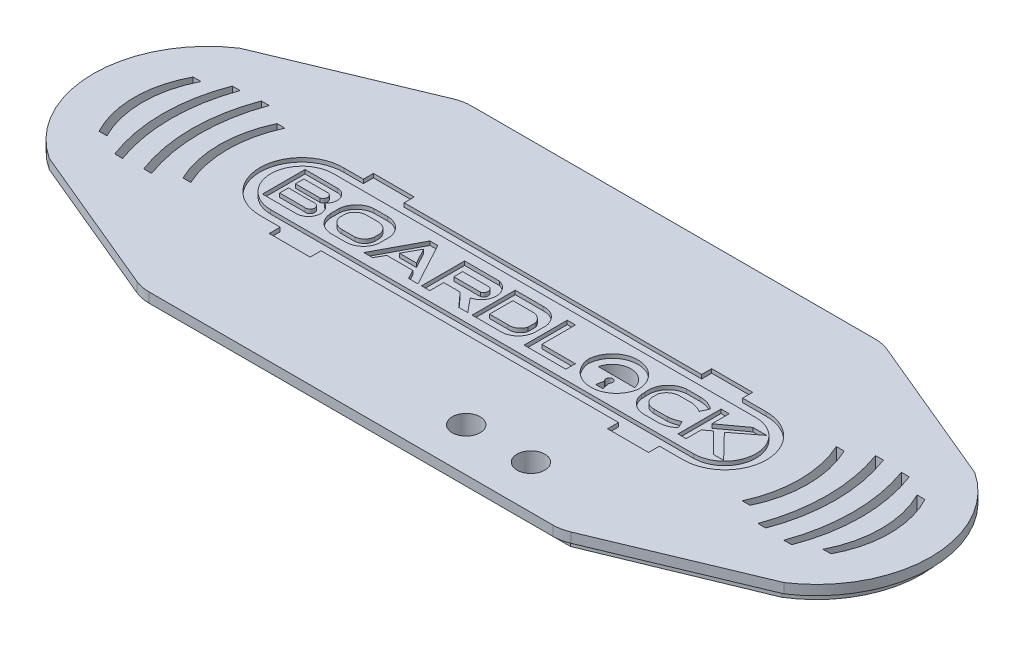
SolidWorks part; units mm, degrees
ref_plane "Front Plane" through (0, 0, 0) normal (0, 0, 1) x (1, 0, 0)
ref_plane "Top Plane" through (0, 0, 0) normal (0, 1, 0) x (1, 0, 0)
ref_plane "Right Plane" through (0, 0, 0) normal (1, 0, 0) x (0, 0, -1)
sketch "Sketch2" plane through (0, 0, 0) normal (0, 1, 0) x (1, 0, 0)
  line L0 (0, 0) -> (102, 0) construction
  line L1 (0, 0) -> (0, -77.2) construction
  line L2 (102, 0) -> (102, -77.2) construction
  line L3 (0, -77.2) -> (102, -77.2) construction
  line L4 (51, 0) -> (51, -77.2) construction
  line L5 (0, -38.6) -> (102, -38.6) construction
  line L6 (-2.5, 2.5) -> (104.5, 2.5)
  line L7 (-2.5, -79.7) -> (104.5, -79.7)
  line L8 (104.5, 2.5) -> (144.7372, -14.2911)
  line L9 (104.5, -79.7) -> (144.7372, -62.9089)
  line L10 (102, -38.6) -> (155.3, -38.6) construction
  line L11 (-2.5, -79.7) -> (-42.7372, -62.9089)
  line L12 (-2.5, 2.5) -> (-42.7372, -14.2911)
  line L13 (0, 0) -> (102, 0)
  line L14 (102, 0) -> (104.5, 0)
  line L15 (104.5, 0) -> (142.7026, -15.7437)
  line L16 (104.5, -77.2) -> (142.7026, -61.4563)
  line L17 (102, -77.2) -> (104.5, -77.2)
  line L18 (-2.5, -77.2) -> (-40.7026, -61.4563)
  line L19 (0, -77.2) -> (-2.5, -77.2)
  line L20 (-2.5, 0) -> (-40.7026, -15.7437)
  line L21 (0, 0) -> (-2.5, 0)
  line L22 (0, -77.2) -> (102, -77.2)
  line L23 (0.5, 0) -> (0.5, -77.2) construction
  line L24 (0, -76.7) -> (97.7329, -76.7) construction
  line L25 (0.5, -74.6) -> (97.3633, -74.6) construction
  line L26 (63.32, -77.2) -> (63.32, 0) construction
  line L27 (0.5, -62.6) -> (97.044, -62.6) construction
  line L28 (75.32, -62.6) -> (75.32, -74.6) construction
  line L29 (79.83, -62.6) -> (79.83, -74.6) construction
  line L30 (91.83, -62.6) -> (91.83, -74.6) construction
  line L31 (69.32, -62.6) -> (69.32, -74.6) construction
  line L32 (63.32, -68.6) -> (75.32, -68.6) construction
  line L33 (85.83, -62.6) -> (85.83, -74.6) construction
  line L34 (79.83, -68.6) -> (91.83, -68.6) construction
  arc A0 (144.7372, -14.2911) -> (144.7372, -62.9089) centre (128.65, -38.6) cw
  arc A1 (-42.7372, -14.2911) -> (-42.7372, -62.9089) centre (-26.65, -38.6) ccw
  arc A2 (142.7026, -15.7437) -> (142.7026, -61.4563) centre (128.65, -38.6) cw
  arc A3 (-40.7026, -15.7437) -> (-40.7026, -61.4563) centre (-26.65, -38.6) ccw
  circle A4 centre (69.32, -68.6) radius 3.55
  circle A5 centre (85.83, -68.6) radius 3.55
  point P16 (157.8, -38.6)
  dimension "D3" = 2.5
  dimension "D10" = 2.5
  dimension "D1" = 77.2
  dimension "D2" = 102
  dimension "D4" = 2.5
  dimension "D5" = 2.5
  dimension "D6" = 2.5
  dimension "D7" = 0.5
  dimension "D8" = 2.5
  dimension "D9" = 53.3
  dimension "D11" = 0.5
  dimension "D12" = 2.1
  dimension "D13" = 62.82
  dimension "D14" = 12
  dimension "D15" = 12
  dimension "D16" = 4.51
  dimension "D17" = 12
  dimension "D18" = 6
  dimension "D19" = 6
  dimension "D20" = 6
  dimension "D21" = 6
extrude "Boss-Extrude3" add sketch "Sketch2" along normal blind 2.5 contours L6 L8 A0 L9 L7 L11 A1 L12
extrude "Boss-Extrude4" add sketch "Sketch2<8>" against normal blind 2.5 contours L20 A3 L18 L19 L22 L17 L16 A2 L15 L14 L13 L21 region at (50.8464, 0, 38.4266)
sketch "Sketch2<8>" plane through (0, 0, 0) normal (0, 1, 0) x (1, 0, 0) same geometry as "Sketch2"
sketch "Sketch3" plane through (0, 2.5, 0) normal (0, 1, 0) x (1, 0, 0)
  line L0 (-55.8, -38.6) -> (157.8, -38.6) construction
  line L1 (51, 2.5) -> (51, -79.7) construction
  line L2 (-2.5, 2.5) -> (104.5, 2.5) construction
  line L3 (-2.5, -79.7) -> (104.5, -79.7) construction
  line L4 (201.4283, 144.6262) -> (1084.095, 144.6262) construction
  line L5 (-2.9873, -27.462) -> (1.9495, -27.462)
  line L6 (1.9495, -27.462) -> (1.9495, -24.9021)
  line L7 (1.9495, -24.9021) -> (12.3717, -24.9021)
  line L8 (12.3717, -24.9021) -> (12.3717, -27.462)
  line L9 (12.3717, -27.462) -> (88.2398, -27.462)
  line L10 (88.2398, -27.462) -> (88.2398, -24.9021)
  line L11 (88.2398, -24.9021) -> (98.6886, -24.9021)
  line L12 (98.6886, -24.9021) -> (98.6886, -27.462)
  line L13 (98.6886, -27.462) -> (104.6245, -27.462)
  line L14 (104.6245, -48.6746) -> (98.6886, -48.6746)
  line L15 (98.6886, -48.6746) -> (98.6886, -51.4646)
  line L16 (98.6886, -51.4646) -> (88.2398, -51.4646)
  line L17 (88.2398, -51.4646) -> (88.2398, -48.6746)
  line L18 (88.2398, -48.6746) -> (12.3717, -48.6746)
  line L19 (12.3717, -48.6746) -> (12.3717, -51.4646)
  line L20 (12.3717, -51.4646) -> (1.9495, -51.4646)
  line L21 (1.9495, -51.4646) -> (1.9495, -48.6746)
  line L22 (1.9495, -48.6746) -> (-2.9873, -48.6746)
  line L23 (-2.9873, -30.0692) -> (104.7002, -30.0692)
  line L24 (104.7002, -46.0158) -> (-3.1948, -46.0158)
  line L25 (-7.6306, -32.7625) -> (-7.6306, -43.6232)
  line L26 (-7.6306, -43.6232) -> (1.1441, -43.6232)
  line L27 (-7.6306, -32.7625) -> (0.7133, -32.7625)
  line L28 (5.3465, -39.2139) -> (5.3465, -36.9174)
  line L29 (-5.6807, -35.0072) -> (0.6, -35.0072)
  line L30 (-5.6807, -35.0072) -> (-5.6807, -37.1385)
  line L31 (-5.6807, -37.1385) -> (0.6, -37.1385)
  line L33 (-5.6807, -38.9524) -> (0.7133, -38.9524)
  line L34 (-5.6807, -38.9524) -> (-5.6807, -41.1744)
  line L35 (-5.6807, -41.1744) -> (0.7133, -41.1744)
  line L41 (10.1371, -35.0072) -> (13.3467, -35.0072)
  line L42 (9.866, -32.6184) -> (13.2281, -32.6184)
  line L43 (18.2229, -43.6232) -> (20.4629, -43.6232)
  line L44 (18.0967, -36.7888) -> (18.0967, -39.563)
  line L45 (16.1379, -37.4286) -> (16.1379, -38.7874)
  line L46 (13.8283, -43.6232) -> (10.2518, -43.6232)
  line L47 (20.4629, -43.6232) -> (21.7662, -41.3167)
  line L48 (13.6087, -41.3167) -> (10.2917, -41.3167)
  line L49 (21.7662, -41.3167) -> (28.4046, -41.3167)
  line L50 (7.3404, -38.9659) -> (7.3404, -37.4286)
  line L51 (28.4046, -41.3167) -> (29.6467, -43.6232)
  line L52 (29.6467, -43.6232) -> (32.0292, -43.6232)
  line L53 (32.0292, -43.6232) -> (26.1026, -32.6184)
  line L54 (26.1026, -32.6184) -> (24.0876, -32.6184)
  line L55 (24.0876, -32.6184) -> (18.2229, -43.6232)
  line L56 (22.9065, -39.2139) -> (27.2439, -39.2139)
  line L57 (27.2439, -39.2139) -> (25.0951, -35.224)
  line L58 (25.0951, -35.224) -> (22.9065, -39.2139)
  line L59 (32.928, -32.6184) -> (32.928, -43.6232)
  line L60 (32.928, -43.6232) -> (35.043, -43.6232)
  line L61 (35.043, -43.6232) -> (35.043, -40.0634)
  line L62 (35.043, -40.0634) -> (39.244, -40.0634)
  line L63 (39.244, -40.0634) -> (42.431, -43.6232)
  line L64 (42.431, -43.6232) -> (44.7378, -43.6232)
  line L65 (44.7378, -43.6232) -> (41.7936, -40.0634)
  line L66 (32.928, -32.6184) -> (41.7936, -32.6184)
  line L67 (35.043, -35.224) -> (35.043, -37.4805)
  line L68 (35.043, -37.4805) -> (41.7936, -37.4805)
  line L69 (35.043, -35.224) -> (41.7936, -35.224)
  line L70 (45.8463, -32.6184) -> (45.8463, -43.6232)
  line L71 (45.8463, -43.6232) -> (52.8329, -43.6232)
  line L72 (45.8463, -32.6184) -> (52.9687, -32.6184)
  line L73 (57.6458, -36.7888) -> (57.6458, -39.563)
  line L74 (47.8647, -35.224) -> (47.8647, -41.1744)
  line L75 (47.8647, -41.1744) -> (52.6, -41.1744)
  line L76 (47.8647, -35.224) -> (52.6, -35.224)
  line L77 (55.6246, -37.1385) -> (55.6246, -39.1866)
  line L78 (59.1096, -32.6184) -> (59.1096, -43.6232)
  line L79 (59.1096, -43.6232) -> (69.7525, -43.6232)
  line L80 (69.7525, -43.6232) -> (69.7525, -41.1876)
  line L81 (69.7525, -41.1876) -> (61.1954, -41.1876)
  line L82 (61.1954, -41.1876) -> (61.1954, -32.6184)
  line L83 (61.1954, -32.6184) -> (59.1096, -32.6184)
  line L84 (72.3273, -37.9056) -> (81.6057, -37.9056)
  line L85 (76.285, -40.2528) -> (75.9572, -42.1923)
  line L86 (75.9572, -42.1923) -> (77.8461, -42.1923)
  line L87 (77.8461, -42.1923) -> (77.3335, -40.2528)
  line L88 (90.3322, -35.0072) -> (93.3549, -35.0072)
  line L89 (96.0824, -35.9398) -> (96.9798, -33.9561)
  line L90 (92.9888, -32.6184) -> (89.5293, -32.6184)
  line L91 (86.9671, -37.333) -> (86.9671, -38.6)
  line L92 (86.9671, -38.6) -> (86.9671, -39.0585)
  line L93 (89.7665, -41.1876) -> (93.2664, -41.1876)
  line L94 (96.1597, -40.3804) -> (97.0399, -42.1923)
  line L95 (93.0498, -43.6232) -> (90.1278, -43.6232)
  line L96 (84.9417, -38.6) -> (84.9417, -39.5139)
  line L97 (98.3461, -32.6195) -> (98.3461, -43.6259)
  line L98 (98.3461, -43.6259) -> (100.4335, -43.6259)
  line L99 (100.4335, -43.6259) -> (100.4335, -39.7387)
  line L100 (100.4335, -39.7387) -> (102.2231, -38.4318)
  line L101 (102.2231, -38.4318) -> (107.3754, -43.6259)
  line L102 (107.3754, -43.6259) -> (110.0073, -43.6259)
  line L103 (110.0073, -43.6259) -> (103.904, -37.333)
  line L104 (103.904, -37.333) -> (110.0073, -32.6195)
  line L105 (110.0073, -32.6195) -> (106.4905, -32.6195)
  line L106 (106.4905, -32.6195) -> (100.4335, -37.0424)
  line L107 (100.4335, -37.0424) -> (100.4335, -32.6195)
  line L108 (100.4335, -32.6195) -> (98.3461, -32.6195)
  arc A0 (86.9671, -37.333) -> (90.3322, -35.0072) centre (90.1278, -38.3088) cw
  arc A1 (93.3549, -35.0072) -> (96.0824, -35.9398) centre (92.5616, -41.7819) cw
  arc A2 (-42.7372, -14.2911) -> (-42.7372, -62.9089) centre (-26.65, -38.6) ccw construction
  arc A3 (144.7372, -62.9089) -> (144.7372, -14.2911) centre (128.65, -38.6) ccw construction
  arc A4 (-2.9873, -27.462) -> (-2.9873, -48.6746) centre (-3.1948, -38.0683) ccw
  arc A5 (104.6245, -27.462) -> (104.6245, -48.6746) centre (104.776, -38.0683) cw
  arc A6 (-2.9873, -30.0692) -> (-3.1948, -46.0158) centre (-3.091, -38.0425) ccw
  arc A7 (104.7002, -30.0692) -> (104.7002, -46.0158) centre (104.7002, -38.0425) cw
  arc A8 (0.7133, -32.7625) -> (2.2325, -37.6827) centre (0.6, -35.492) cw
  arc A9 (1.1441, -43.6232) -> (2.2325, -37.6827) centre (1.0303, -40.5324) ccw
  arc A10 (0.6, -35.0072) -> (0.6, -37.1385) centre (0.3019, -36.0728) cw
  arc A11 (0.7133, -41.1744) -> (0.7133, -38.9524) centre (0.9838, -40.0634) ccw
  arc A12 (5.3465, -36.9174) -> (9.866, -32.6184) centre (10.1371, -37.4286) cw
  arc A13 (18.0967, -36.7888) -> (13.2281, -32.6184) centre (13.2836, -37.4805) ccw
  arc A14 (5.3465, -39.2139) -> (10.2518, -43.6232) centre (10.0037, -38.9659) ccw
  arc A15 (13.8283, -43.6232) -> (18.0967, -39.563) centre (13.6087, -39.1187) ccw
  arc A16 (10.1371, -35.0072) -> (7.3404, -37.4286) centre (10.2483, -37.9613) ccw
  arc A17 (13.3467, -35.0072) -> (16.1379, -37.4286) centre (13.2781, -37.9056) cw
  arc A18 (16.1379, -38.7874) -> (13.6087, -41.3167) centre (13.3904, -38.5692) cw
  arc A19 (10.2917, -41.3167) -> (7.3404, -38.9659) centre (10.2917, -38.2887) cw
  arc A20 (41.7936, -35.224) -> (41.7936, -37.4805) centre (41.488, -36.3523) cw
  arc A21 (41.7936, -40.0634) -> (41.7936, -32.6184) centre (40.9073, -36.3409) ccw
  arc A22 (52.9687, -32.6184) -> (57.6458, -36.7888) centre (53.222, -37.0421) cw
  arc A23 (57.6458, -39.563) -> (52.8329, -43.6232) centre (53.2093, -39.1866) cw
  arc A24 (52.6, -35.224) -> (55.6246, -37.1385) centre (52.8789, -38.1299) cw
  arc A25 (55.6246, -39.1866) -> (52.6, -41.1744) centre (52.8755, -38.2986) cw
  arc A26 (70.3877, -38.6) -> (83.4404, -38.6) centre (76.9141, -38.8997) cw
  arc A27 (70.3877, -38.6) -> (83.4404, -38.6) centre (76.9141, -37.8504) ccw
  arc A28 (76.285, -40.2528) -> (77.3335, -40.2528) centre (76.8092, -39.581) cw
  arc A29 (72.3273, -37.9056) -> (81.6057, -37.9056) centre (76.9665, -38.9919) cw
  arc A30 (96.9798, -33.9561) -> (92.9888, -32.6184) centre (93.0498, -39.0585) ccw
  arc A31 (89.5293, -32.6184) -> (84.9417, -38.6) centre (89.9999, -37.7293) ccw
  arc A32 (86.9671, -39.0585) -> (89.7665, -41.1876) centre (89.6538, -38.4308) ccw
  arc A33 (93.2664, -41.1876) -> (96.1597, -40.3804) centre (92.4973, -32.8415) ccw
  arc A34 (84.9417, -39.5139) -> (90.1278, -43.6232) centre (89.7907, -38.7214) ccw
  arc A35 (93.0498, -43.6232) -> (97.0399, -42.1923) centre (93.1901, -37.7354) ccw
extrude "Logo" cut sketch "Sketch3" against normal blind 1 contours L26 A9 A8 L27 L25 A11 L35 L34 L33 L29 A10 L31 L30 | L46 A15 L44 A13 L42 A12 L28 A14 L48 A19 L50 A16 L41 A17 L45 A18 | L54 L55 L43 L47 L49 L51 L52 L53 L58 L57 L56 | L65 A21 L66 L59 L60 L61 L62 L63 L64 L69 A20 L68 L67 | A23 L73 A22 L72 L70 L71 L77 A25 L75 L74 L76 A24 | A26 A27 L85 A28 L87 L86 L84 A29 | L95 A35 L94 A33 L93 A32 L92 L91 A0 L88 A1 L89 A30 L90 A31 L96 A34 | L107 L108 L97 L98 L99 L100 L101 L102 L103 L104 L105 L106 | L82 L83 L78 L79 L80 L81 | A4 L22 L21 L20 L19 L18 L17 L16 L15 L14 A5 L13 L12 L11 L10 L9 L8 L7 L6 L5 | A6 L24 A7 L23 | L78 L79 L80 L81 L82 L83 region at (-2.2321, 2.5, 38.3038) region at (5.5149, 2.5, 38.0657) region at (21.3111, 2.5, 38.2038) region at (37.3608, 2.5, 32.7798) region at (49.4075, 2.5, 32.7799) region at (60.1525, 2.5, 32.7715) region at (88.1536, 2.5, 35.4525) region at (102.8661, 2.5, 37.8921) region at (76.9141, 2.5, 32.5442)
fillet "Fillet1" radius 10 4 edges at (-2.5, 1.25, -2.5) (104.5, 1.25, -2.5) (104.5, 1.25, 79.7) (-2.5, 1.25, 79.7)
sketch "Sketch4" plane through (0, 2.5, 0) normal (0, 1, 0) x (1, 0, 0)
  line L0 (-55.8, -38.6) -> (157.8, -38.6) construction
  line L1 (51, 2.5) -> (51, -79.7) construction
  line L2 (-0.4972, 2.5) -> (102.4972, 2.5) construction
  line L3 (-0.4972, -79.7) -> (102.4972, -79.7) construction
  line L4 (-42.3364, -26.6) -> (-42.3364, -50.6) construction
  line L5 (-40.3364, -26.6) -> (-40.3364, -50.6) construction
  line L6 (-35.3364, -23.6) -> (-35.3364, -53.6) construction
  line L7 (-33.3364, -23.6) -> (-33.3364, -53.6) construction
  line L8 (-28.3364, -23.2) -> (-28.3364, -53.2) construction
  line L9 (-26.3364, -23.2) -> (-26.3364, -53.2) construction
  line L10 (-21.3364, -26.2) -> (-21.3364, -50.2) construction
  line L11 (-19.3364, -26.2) -> (-19.3364, -50.2) construction
  line L12 (-42.3364, -26.6) -> (-40.3364, -26.6)
  line L13 (-42.3364, -50.6) -> (-40.3364, -50.6)
  line L14 (-35.3364, -53.6) -> (-33.3364, -53.6)
  line L15 (-35.3364, -23.6) -> (-33.3364, -23.6)
  line L16 (-28.3364, -23.2) -> (-26.3364, -23.2)
  line L17 (-28.3364, -53.2) -> (-26.3364, -53.2)
  line L18 (-21.3364, -50.2) -> (-19.3364, -50.2)
  line L19 (-21.3364, -26.2) -> (-19.3364, -26.2)
  line L20 (121.3364, -26.2) -> (121.3364, -50.2) construction
  line L21 (123.3364, -26.2) -> (123.3364, -50.2) construction
  line L22 (128.3364, -23.2) -> (128.3364, -53.2) construction
  line L23 (130.3364, -23.2) -> (130.3364, -53.2) construction
  line L24 (135.3364, -23.6) -> (135.3364, -53.6) construction
  line L25 (137.3364, -23.6) -> (137.3364, -53.6) construction
  line L26 (142.3364, -26.6) -> (142.3364, -50.6) construction
  line L27 (144.3364, -26.6) -> (144.3364, -50.6) construction
  line L28 (123.3364, -26.2) -> (121.3364, -26.2)
  line L29 (123.3364, -50.2) -> (121.3364, -50.2)
  line L30 (130.3364, -53.2) -> (128.3364, -53.2)
  line L31 (130.3364, -23.2) -> (128.3364, -23.2)
  line L32 (137.3364, -23.6) -> (135.3364, -23.6)
  line L33 (137.3364, -53.6) -> (135.3364, -53.6)
  line L34 (144.3364, -50.6) -> (142.3364, -50.6)
  line L35 (144.3364, -26.6) -> (142.3364, -26.6)
  arc A0 (-42.7372, -14.2911) -> (-42.7372, -62.9089) centre (-26.65, -38.6) ccw construction
  arc A1 (144.7372, -62.9089) -> (144.7372, -14.2911) centre (128.65, -38.6) ccw construction
  arc A2 (-42.3364, -26.6) -> (-42.3364, -50.6) centre (-19.91, -38.6) ccw
  arc A3 (-40.3364, -26.6) -> (-40.3364, -50.6) centre (-16.7181, -38.6) ccw
  arc A4 (-35.3364, -23.6) -> (-35.3364, -53.6) centre (3.8054, -38.6) ccw
  arc A5 (-33.3364, -53.6) -> (-33.3364, -23.6) centre (8.2465, -38.6) cw
  arc A6 (-28.3364, -23.2) -> (-28.3364, -53.2) centre (11.3609, -38.2) ccw
  arc A7 (-26.3364, -23.2) -> (-26.3364, -53.2) centre (14.8909, -38.2) ccw
  arc A8 (-21.3364, -26.2) -> (-21.3364, -50.2) centre (3.9499, -38.2) ccw
  arc A9 (-19.3364, -26.2) -> (-19.3364, -50.2) centre (6.9686, -38.2) ccw
  arc A10 (121.3364, -26.2) -> (121.3364, -50.2) centre (95.0314, -38.2) cw
  arc A11 (123.3364, -26.2) -> (123.3364, -50.2) centre (98.0501, -38.2) cw
  arc A12 (128.3364, -23.2) -> (128.3364, -53.2) centre (87.1091, -38.2) cw
  arc A13 (130.3364, -23.2) -> (130.3364, -53.2) centre (90.6391, -38.2) cw
  arc A14 (135.3364, -53.6) -> (135.3364, -23.6) centre (93.7535, -38.6) ccw
  arc A15 (137.3364, -23.6) -> (137.3364, -53.6) centre (98.1946, -38.6) cw
  arc A16 (142.3364, -26.6) -> (142.3364, -50.6) centre (118.7181, -38.6) cw
  arc A17 (144.3364, -26.6) -> (144.3364, -50.6) centre (121.91, -38.6) cw
  dimension "D1" = 24
  dimension "D2" = 12
  dimension "D3" = 30
  dimension "D4" = 15
  dimension "D5" = 2
  dimension "D6" = 2
  dimension "D7" = 2
  dimension "D8" = 2
  dimension "D9" = 7
  dimension "D10" = 7
  dimension "D11" = 7
extrude "SoundGaps" cut sketch "Sketch4" against normal up to next
sketch "Sketch5" plane through (0, 2.5, 0) normal (0, 1, 0) x (1, 0, 0)
  circle A2 centre (69.32, -68.6) radius 3.55
  circle A3 centre (85.83, -68.6) radius 3.55
extrude "Buttons" cut sketch "Sketch5" against normal up to next
extrude "Cut-Extrude5" cut sketch "Sketch3<5>" against normal up to next contours A29 L84 | L85 L86 L87 A28 region at (76.9665, 2.5, 36.3712)
sketch "Sketch3<5>" plane through (0, 2.5, 0) normal (0, 1, 0) x (1, 0, 0) same geometry as "Sketch3"
